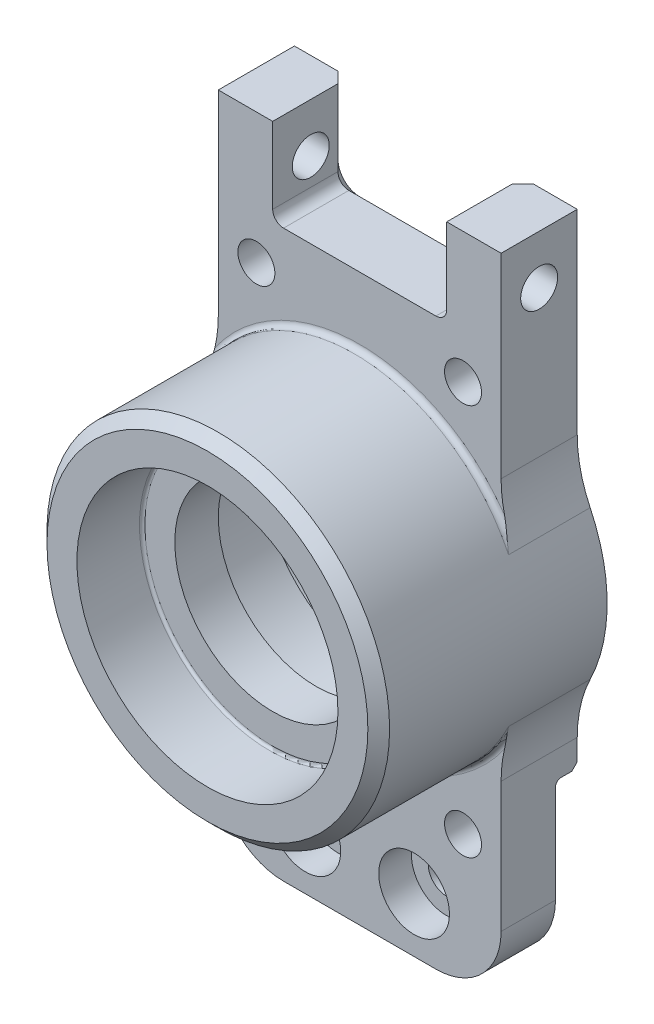
SolidWorks part; units mm, degrees
material "6061 Alloy"
ref_plane "Front Plane" through (0, 0, 0) normal (0, 0, 1) x (1, 0, 0)
ref_plane "Top Plane" through (0, 0, 0) normal (0, 1, 0) x (1, 0, 0)
ref_plane "Right Plane" through (0, 0, 0) normal (1, 0, 0) x (0, 0, -1)
sketch "Sketch1" plane through (0, 0, 0) normal (0, 0, 1) x (1, 0, 0)
  circle A0 centre (0, 0) radius 15.75
  dimension "D1" = 31.5
extrude "Boss-Extrude1" add sketch "Sketch1" along normal blind 21
sketch "Sketch2" plane through (0, 0, 0) normal (0, 0, -1) x (-1, 0, 0)
  line L1 (-13, 30) -> (13, 30)
  line L2 (-13, 30) -> (-13, -30)
  line L3 (-13, -30) -> (13, -30)
  line L4 (13, 30) -> (13, -30)
  dimension "D1" = 60
  dimension "D2" = 26
  dimension "D3" = 13
  dimension "D4" = 30
extrude "Boss-Extrude2" add sketch "Sketch2" against normal blind 7
sketch "Sketch3" plane through (0, 0, 0) normal (0, 0, -1) x (-1, 0, 0)
  circle A0 centre (0, 0) radius 13
  dimension "D1" = 26
extrude "Cut-Extrude1" cut sketch "Sketch3" against normal blind 5
sketch "Sketch4" plane through (0, 0, 5) normal (0, 0, -1) x (-1, 0, 0)
  circle A0 centre (0, 0) radius 11
  dimension "D1" = 22
extrude "Cut-Extrude2" cut sketch "Sketch4" against normal blind 6
sketch "Sketch6" plane through (0, 30, 0) normal (0, 1, 0) x (1, 0, 0)
  line L0 (-13, -7) -> (13, -7) construction
  line L1 (8, -7) -> (-8, -7)
  line L2 (8, -7) -> (8, 0)
  line L3 (8, 0) -> (-8, 0)
  line L4 (-8, -7) -> (-8, 0)
  line L5 (-13, 0) -> (13, 0) construction
  line L6 (-13, -7) -> (-13, 0) construction
  line L7 (13, -7) -> (13, 0) construction
  dimension "D1" = 5
  dimension "D2" = 5
extrude "Cut-Extrude4" cut sketch "Sketch6" against normal blind 8
hole_wizard "M3 Clearance Hole1" positions "Sketch7" profile "Sketch8" hole size "M3" standard "ANSI Metric" end condition through all
sketch "Sketch7" plane through (0, 0, 7) normal (0, 0, 1) x (1, 0, 0)
  line L0 (-13, 8.8917) -> (-13, 30) construction
  line L1 (13, 30) -> (13, 8.8917) construction
  line L2 (-13, -30) -> (-13, -8.8917) construction
  line L3 (13, -8.8917) -> (13, -30) construction
  point P0 (-9.5, 18)
  point P2 (9.5, 18)
  point P4 (-9.5, -18)
  point P6 (9.5, -18)
  dimension "D1" = 18
  dimension "D2" = 18
  dimension "D3" = 18
  dimension "D4" = 18
  dimension "D5" = 3.5
  dimension "D6" = 3.5
  dimension "D7" = 3.5
  dimension "D8" = 3.5
sketch "Sketch8" plane through (-9.5, 18, 7) normal (1, 0, 0) x (0, -1, 0)
  line L0 (0, 0) -> (0, 7)
  line L1 (0, 7) -> (1.7, 7)
  line L2 (1.7, 7) -> (1.7, 0)
  line L5 (1.7, 0) -> (0, 0)
  line L11 (0, -6.35) -> (0, 107.95) construction
  dimension "Thru Hole Dia." = 3.4
  dimension "Thru Hole Depth" = 7
hole_wizard "M3 Clearance Hole2" positions "Sketch9" profile "Sketch10" hole size "M3" standard "ANSI Metric" end condition through all
sketch "Sketch9" plane through (13, 0, 0) normal (1, 0, 0) x (0, 0, -1)
  line L0 (-7, 30) -> (0, 30) construction
  line L1 (-7, 30) -> (-7, 8.8917) construction
  point P0 (-3.5, 25.5)
  dimension "D1" = 4.5
  dimension "D2" = 3.5
sketch "Sketch10" plane through (13, 25.5, 3.5) normal (0, 1, 0) x (0, 0, -1)
  line L0 (0, 0) -> (0, 28.75)
  line L1 (0, 28.75) -> (1.7, 28.75)
  line L2 (1.7, 28.75) -> (1.7, 0)
  line L5 (1.7, 0) -> (0, 0)
  line L11 (0, -6.35) -> (0, 107.95) construction
  dimension "Thru Hole Dia." = 3.4
  dimension "Thru Hole Depth" = 28.75
sketch "Sketch11" plane through (0, 0, 0) normal (0, 0, -1) x (-1, 0, 0)
  line L0 (13, -30) -> (13, -8.8917) construction
  line L1 (-13, -30) -> (13, -30)
  line L2 (-13, -30) -> (-13, -14.5)
  line L3 (-13, -14.5) -> (13, -14.5)
  line L4 (13, -30) -> (13, -14.5)
  dimension "D1" = 14.5
extrude "Cut-Extrude5" cut sketch "Sketch11" against normal blind 2
sketch "Sketch12" plane through (0, 0, 7) normal (0, 0, 1) x (1, 0, 0)
  line L0 (13, -30) -> (-13, -30) construction
  line L1 (-13, -30) -> (-13, -8.8917) construction
  line L2 (13, -8.8917) -> (13, -30) construction
  circle A0 centre (-5, -25) radius 3.25
  circle A1 centre (5, -25) radius 3.25
  dimension "D1" = 6.5
  dimension "D2" = 6.5
  dimension "D3" = 5
  dimension "D4" = 5
  dimension "D5" = 8
  dimension "D6" = 8
extrude "Cut-Extrude6" cut sketch "Sketch12" against normal blind 3
hole_wizard "M3 Clearance Hole3" positions "Sketch13" profile "Sketch14" hole size "M3" standard "ANSI Metric" end condition through all
sketch "Sketch13" plane through (0, 0, 4) normal (0, 0, 1) x (1, 0, 0)
  circle A2 centre (5, -25) radius 3.25 construction
  circle A3 centre (-5, -25) radius 3.25 construction
  point P0 (-5, -25)
  point P2 (5, -25)
sketch "Sketch14" plane through (-5, -25, 4) normal (1, 0, 0) x (0, -1, 0)
  line L0 (0, 0) -> (0, 4)
  line L1 (0, 4) -> (1.7, 4)
  line L2 (1.7, 4) -> (1.7, 0)
  line L5 (1.7, 0) -> (0, 0)
  line L11 (0, -6.35) -> (0, 107.95) construction
  dimension "Thru Hole Dia." = 3.4
  dimension "Thru Hole Depth" = 4
sketch "Sketch15" plane through (0, 0, 21) normal (0, 0, 1) x (1, 0, 0)
  circle A0 centre (0, 0) radius 12
  dimension "D1" = 24
extrude "Cut-Extrude7" cut sketch "Sketch15" against normal blind 6
sketch "Sketch16" plane through (0, 0, 15) normal (0, 0, 1) x (1, 0, 0)
  circle A0 centre (0, 0) radius 9
  dimension "D1" = 18
extrude "Cut-Extrude8" cut sketch "Sketch16" against normal through all
chamfer "Chamfer1" distance 0.5 angle 45 1 edges at (0, -14.5, 0)
fillet "Fillet1" radius 0.5 1 edges at (0, -14.5, 2)
fillet "Fillet2" radius 6 2 edges at (13, -30, 4.5) (-13, -30, 4.5)
fillet "Fillet3" radius 12 4 edges at (13, -8.8917, 3.5) (13, 8.8917, 3.5) (-13, -8.8917, 3.5) (-13, 8.8917, 3.5)
fillet "Fillet4" radius 0.5 2 edges at (0, -15.75, 7) (0, 15.75, 7)
fillet "Fillet5" radius 1 2 edges at (-8, 22, 3.5) (8, 22, 3.5)
fillet "Fillet7" radius 0.25 1 edges at (12, 0, 15)
chamfer "Chamfer2" distance 1 angle 45 1 edges at (15.75, 0, 21)
fillet "Fillet8" radius 0.25 1 edges at (-11, 0, 11)
fillet "Fillet9" radius 1 1 edges at (-13, 0, 5)
chamfer "Chamfer4" distance 1 angle 45 5 edges at (8, 26.5, 0) (-8, 26.5, 0) (7.7071, 22.2929, 0) (-7.7071, 22.2929, 0) (0, 22, 0)
